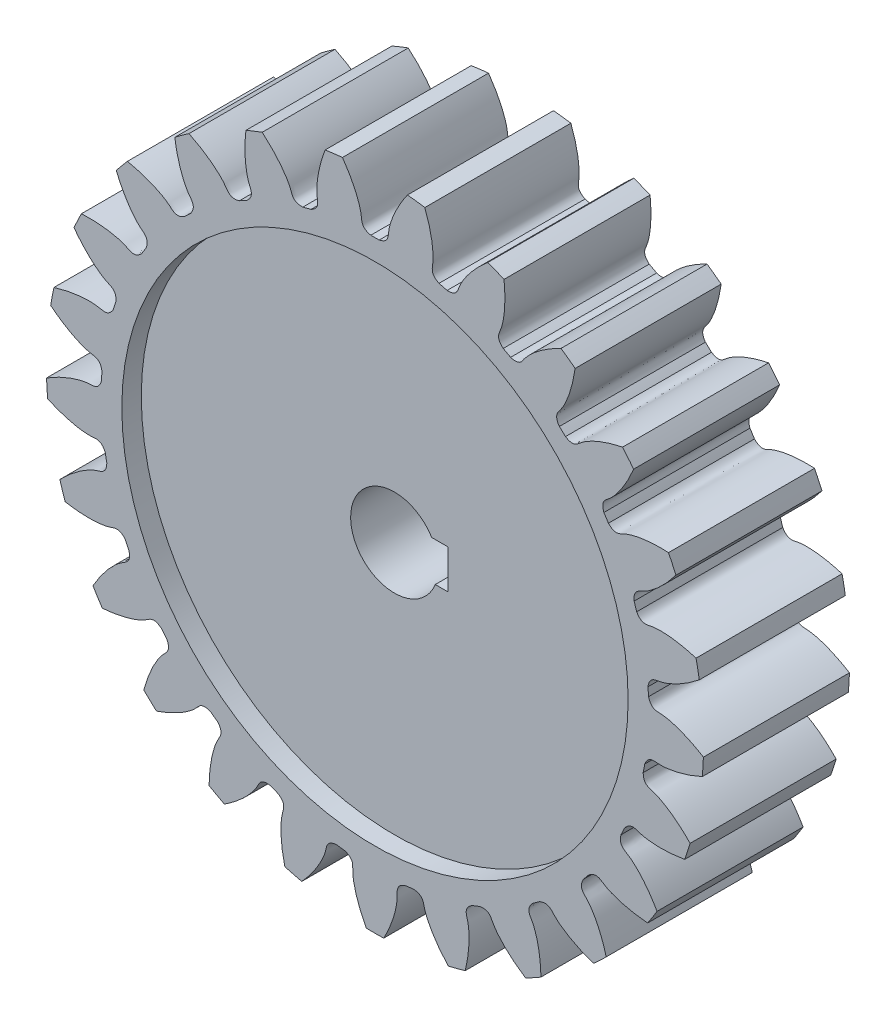
SolidWorks part; units mm, degrees
ref_plane "前视基准面" through (0, 0, 0) normal (0, 0, 1) x (1, 0, 0)
ref_plane "上视基准面" through (0, 0, 0) normal (0, 1, 0) x (1, 0, 0)
ref_plane "右视基准面" through (0, 0, 0) normal (1, 0, 0) x (0, 0, -1)
sketch "草图1" plane through (0, 0, 0) normal (0, 0, 1) x (1, 0, 0)
  circle A0 centre (0, 0) radius 33.75
extrude "凸台-拉伸1" add sketch "草图1" along normal blind 15
ref_axis "基准轴1" through (0, 0, 15) along (0, 0, -1)
sketch "草图2" plane through (0, 0, 0) normal (0, 0, 1) x (1, 0, 0)
  line L0 (0, 0) -> (0, 33.75) construction
  circle A0 centre (0, 0) radius 33.75 construction
  arc A1 (0.4301, 28.1217) -> (-0.4301, 28.1217) centre (0, 0) ccw
  arc A2 (8.0132, 38.2871) -> (-8.0132, 38.2871) centre (0, 0) ccw
  spline S0 degree 3 poles (0.4301, 28.1217) (1.4333, 28.3377) (1.3388, 28.9432) (1.4355, 29.5451) (1.4491, 29.6203) (1.4664, 29.7066) (1.4881, 29.8041) (1.5145, 29.9125) (1.546, 30.0318) (1.5831, 30.1617) (1.6263, 30.302) (1.6759, 30.4526) (1.7324, 30.6133) (1.7963, 30.7838) (1.8679, 30.9639) (1.9476, 31.1534) (2.0358, 31.352) (2.133, 31.5594) (2.2396, 31.7754) (2.3558, 31.9996) (2.4821, 32.2318) (2.6188, 32.4716) (2.7663, 32.7187) (2.925, 32.9728) (3.0951, 33.2335) (3.277, 33.5004) (3.471, 33.7733) (3.6774, 34.0516) (3.8966, 34.335) (4.1287, 34.6232) (4.3741, 34.9157) (4.633, 35.212) (4.9057, 35.5118) (5.1924, 35.8146) (5.4934, 36.12) (5.8088, 36.4275) (6.1389, 36.7366) (6.4838, 37.047) (6.8437, 37.3581) (7.3499, 37.7782) (7.7437, 38.0852) (8.0132, 38.2871) knots 0 0 0 0 0.130741 0.135745 0.141658 0.148481 0.156214 0.164857 0.174409 0.184871 0.196243 0.208524 0.221715 0.235816 0.250827 0.266748 0.283578 0.301318 0.319968 0.339527 0.359996 0.381375 0.403664 0.426862 0.450971 0.475988 0.501916 0.528753 0.556501 0.585157 0.614724 0.6452 0.676587 0.708882 0.742088 0.776203 0.811228 0.847163 0.884008 0.921762 1 1 1 1
  spline S1 degree 3 poles (-0.4301, 28.1217) (-1.4333, 28.3377) (-1.3388, 28.9432) (-1.4355, 29.5451) (-1.4491, 29.6203) (-1.4664, 29.7066) (-1.4881, 29.8041) (-1.5145, 29.9125) (-1.546, 30.0318) (-1.5831, 30.1617) (-1.6263, 30.302) (-1.6759, 30.4526) (-1.7324, 30.6133) (-1.7963, 30.7838) (-1.8679, 30.9639) (-1.9476, 31.1534) (-2.0358, 31.352) (-2.133, 31.5594) (-2.2396, 31.7754) (-2.3558, 31.9996) (-2.4821, 32.2318) (-2.6188, 32.4716) (-2.7663, 32.7187) (-2.925, 32.9728) (-3.0951, 33.2335) (-3.277, 33.5004) (-3.471, 33.7733) (-3.6774, 34.0516) (-3.8966, 34.335) (-4.1287, 34.6232) (-4.3741, 34.9157) (-4.633, 35.212) (-4.9057, 35.5118) (-5.1924, 35.8146) (-5.4934, 36.12) (-5.8088, 36.4275) (-6.1389, 36.7366) (-6.4838, 37.047) (-6.8437, 37.3581) (-7.3499, 37.7782) (-7.7437, 38.0852) (-8.0132, 38.2871) knots 0 0 0 0 0.130741 0.135745 0.141658 0.148481 0.156214 0.164857 0.174409 0.184871 0.196243 0.208524 0.221715 0.235816 0.250827 0.266748 0.283578 0.301318 0.319968 0.339527 0.359996 0.381375 0.403664 0.426862 0.450971 0.475988 0.501916 0.528753 0.556501 0.585157 0.614724 0.6452 0.676587 0.708882 0.742088 0.776203 0.811228 0.847163 0.884008 0.921762 1 1 1 1
extrude "切除-拉伸1" cut sketch "草图2" along normal through all
pattern_circular "阵列(圆周)1" count 25 every 14.4 about axis through (0, 0, 15) along (0, 0, -1) of "切除-拉伸1"
sketch "草图3" plane through (0, 0, 0) normal (0, 0, 1) x (1, 0, 0)
  circle A0 centre (0, 0) radius 31.25 construction
  dimension "Dn" = 62.5
sketch "草图4" plane through (0, 0, 15) normal (0, 0, 1) x (1, 0, 0)
  line L1 (3.8293, 2.3636) -> (5.5, 2.3636)
  line L3 (4.1919, -1.6364) -> (5.5, -1.6364)
  line L4 (5.5, 2.3636) -> (5.5, -1.6364)
  arc A0 (3.8293, 2.3636) -> (4.1919, -1.6364) centre (0, 0) ccw
  point P3 (4.5, 0)
  dimension "D1" = 9
  dimension "D2" = 5.5
  dimension "D3" = 4
extrude "切除-拉伸2" cut sketch "草图4" against normal through all
sketch "草图5" plane through (0, 0, 15) normal (0, 0, 1) x (1, 0, 0)
  circle A0 centre (0, 0) radius 26
  dimension "D1" = 52
extrude "切除-拉伸3" cut sketch "草图5" against normal blind 2
sketch "草图6" plane through (0, 0, 0) normal (0, 0, -1) x (-1, 0, 0)
  circle A0 centre (0, 0) radius 26
  dimension "D1" = 52
extrude "切除-拉伸4" cut sketch "草图6" against normal blind 2
